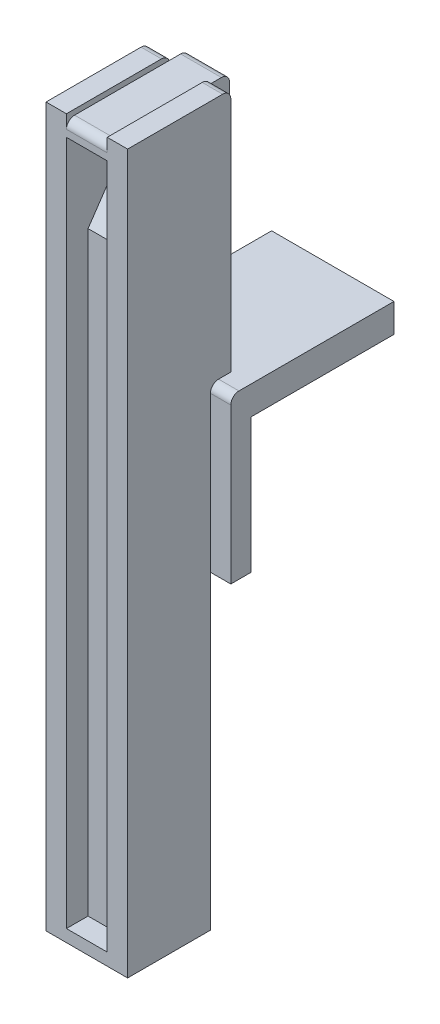
SolidWorks part; units mm, degrees
other "Markup1"
sketch "Sketch9" plane through (15, -116, 20.3) normal (0.0924, -0.1613, 0.9826) x (0.9819, 0.1786, -0.063)
ref_plane "Front Plane" through (0, 0, 0) normal (0, 0, 1) x (1, 0, 0)
ref_plane "Top Plane" through (0, 0, 0) normal (0, 1, 0) x (1, 0, 0)
ref_plane "Right Plane" through (0, 0, 0) normal (1, 0, 0) x (0, 0, -1)
sketch "Sketch2" plane through (0, 0, 0) normal (1, 0, 0) x (0, 0, -1)
  line L0 (0, 0) -> (0, -40)
  line L3 (0, -40) -> (5, -40)
  line L4 (5, -40) -> (5, -7)
  line L5 (5, -7) -> (40, -7)
  line L6 (40, -7) -> (40, 0)
  line L7 (40, 0) -> (0, 0)
  dimension "D1" = 33
  dimension "D2" = 7
  dimension "D3" = 35
  dimension "D4" = 5
extrude "Boss-Extrude2" add sketch "Sketch2" along normal mid plane 30
sketch "Sketch3" plane through (0, 0, 0) normal (1, 0, 0) x (0, 0, -1)
  line L0 (0, -116) -> (-15, -116)
  line L1 (5, -7) -> (40, -7) construction
  line L2 (0, -116) -> (0, 55.0016)
  line L7 (0, 55.0016) -> (-15, 32.9716)
  line L8 (-15, -116) -> (-15, 32.9716)
  dimension "D1" = 109
  dimension "D2" = 22.03
  dimension "D4" = 148.9716
extrude "Boss-Extrude3" add sketch "Sketch3" along normal mid plane 10
sketch "Sketch4" plane through (-5, 0, 0) normal (-1, 0, 0) x (0, 0, 1)
  line L1 (0, 60) -> (20.3, 60)
  line L2 (20.3, 60) -> (20.3, -116)
  line L3 (20.3, -116) -> (0, -116)
  line L6 (0, -116) -> (0, 0)
  line L7 (0, 0) -> (-5, 0)
  line L8 (-40, 0) -> (0, 0) construction
  line L9 (-5, 0) -> (-5, 60)
  line L10 (-5, 60) -> (0, 60)
  dimension "D1" = 5
  dimension "D2" = 60
  dimension "D3" = 176
  dimension "D4" = 20.3
extrude "Boss-Extrude4" add sketch "Sketch4" along normal blind 5 contours L3 L6 L7 L9 L10 L1 L2
mirror "Mirror1" about plane through (0, 0, 0) normal (1, 0, 0) of "Boss-Extrude4"
sketch "Sketch8" plane through (5, 0, 0) normal (-1, 0, 0) x (0, 0, 1)
  line L0 (0, 0) -> (0, 55)
  line L1 (0, 55) -> (20.3, 55)
  line L2 (20.3, 60) -> (20.3, -116) construction
  line L3 (20.3, 55) -> (20.3, 58.7)
  line L4 (20.3, 58.7) -> (-9.7, 58.7)
  line L5 (-9.7, 58.7) -> (-9.7, 0)
  line L6 (0, 0) -> (-5, 0) construction
  line L7 (-9.7, 0) -> (0, 0)
  point P14 (-2.5, 0)
  dimension "D1" = 30
  dimension "D2" = 3.7
  dimension "D3" = 55
extrude "Boss-Extrude5" add sketch "Sketch8" along normal blind 10
sketch "Sketch10" plane through (0, 0, 15) normal (0, 0, 1) x (1, 0, 0)
  line L0 (5, 32.9716) -> (5, -116) construction
  line L1 (-5, -116) -> (5, -116)
  line L2 (-5, -116) -> (-5, -113)
  line L3 (-5, -113) -> (5, -113)
  line L4 (5, -116) -> (5, -113)
  dimension "D1" = 3
extrude "Boss-Extrude6" add sketch "Sketch10" along normal blind 5.3
fillet "Fillet1" radius 2 4 edges at (0, 58.7, 20.3) (0, 58.7, -9.7) (7.5, 60, -5) (-7.5, 60, -5)
fillet "Fillet2" radius 2 2 edges at (-12.5, 0, 0) (12.5, 0, 0)
